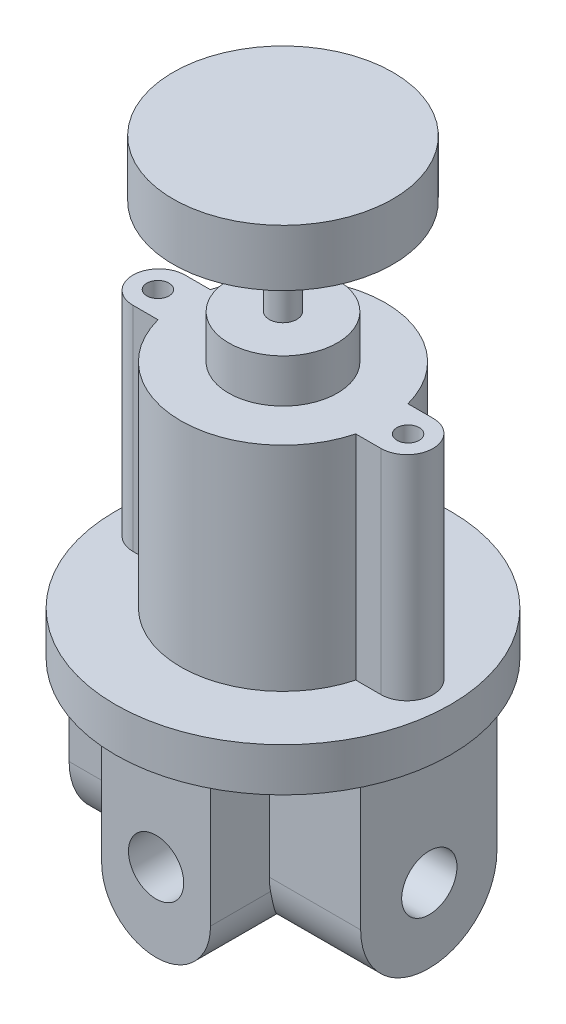
SolidWorks part; units mm, degrees
ref_plane "Front" through (0, 0, 0) normal (0, 0, 1) x (1, 0, 0)
ref_plane "Top" through (0, 0, 0) normal (0, 1, 0) x (1, 0, 0)
ref_plane "Right" through (0, 0, 0) normal (1, 0, 0) x (0, 0, -1)
ref_axis "Axis1" through (0, 0, 55) along (0, 0, -1)
sketch "Sketch1" plane through (0, 0, 0) normal (0, 1, 0) x (1, 0, 0)
  line L0 (-28.5, 0) -> (28.5, 0) construction
  line L1 (-28.5, 6) -> (-22.7211, 6)
  line L2 (-28.5, -6) -> (-22.7211, -6)
  line L3 (-34.5, 0) -> (-34.5, 13.9464) construction
  line L4 (34.5, 0) -> (34.5, 13.318) construction
  line L5 (22.7211, 6) -> (28.5, 6)
  line L6 (22.7211, -6) -> (28.5, -6)
  arc A0 (-22.7211, -6) -> (22.7211, -6) centre (0, 0) ccw
  arc A1 (-28.5, 6) -> (-28.5, -6) centre (-28.5, 0) ccw
  arc A2 (28.5, -6) -> (28.5, 6) centre (28.5, 0) ccw
  arc A3 (22.7211, 6) -> (-22.7211, 6) centre (0, 0) ccw
  point P5 (0, 0)
  dimension "D1" = 47
  dimension "D2" = 12
  dimension "D3" = 69
extrude "Boss-Extrude1" add sketch "Sketch1" against normal blind 49
hole_wizard "1/4-20 Tapped Hole1" positions "Sketch2" profile "Sketch3" tap size "1/4-20" standard "ANSI Inch" end condition up to next
sketch "Sketch2" plane through (0, 0, 0) normal (0, 1, 0) x (1, 0, 0)
  line L0 (34.5, 0) -> (-34.5, 0) construction
  line L2 (0, 0) -> (0, 23.5) construction
  arc A0 (28.5, -6) -> (28.5, 6) centre (28.5, 0) ccw construction
  arc A1 (-28.5, 6) -> (-28.5, -6) centre (-28.5, 0) ccw construction
  arc A2 (22.7211, 6) -> (-22.7211, 6) centre (0, 0) ccw construction
  point P0 (-28.75, 0)
  point P3 (28.75, 0)
  dimension "D1" = 57.5
sketch "Sketch3" plane through (-28.75, 0, 0) normal (1, 0, 0) x (0, 0, 1)
  line L0 (0, 0) -> (0, 49)
  line L1 (0, 49) -> (2.5527, 49)
  line L2 (2.5527, 49) -> (2.5527, 0)
  line L5 (2.5527, 0) -> (0, 0)
  line L11 (0, -6.35) -> (0, 107.95) construction
  dimension "Thru Tap Drill Dia." = 5.1054
  dimension "Thru Tap Drill Depth" = 49
cosmetic thread "Hole Thread1" parameters "D2"=6.35
cosmetic thread "Hole Thread2" parameters "D2"=6.35
sketch "Sketch4" plane through (0, -49, 0) normal (0, -1, 0) x (1, 0, 0)
  circle A0 centre (0, 0) radius 38.5
  dimension "D1" = 77
extrude "Boss-Extrude2" add sketch "Sketch4" along normal blind 10
sketch "Sketch5" plane through (0, -59, 0) normal (0, -1, 0) x (1, 0, 0)
  line L0 (12.5, 15.65) -> (33.5, 15.65)
  line L1 (-33.5, 15.65) -> (-12.5, 15.65)
  line L2 (-33.5, 15.65) -> (-33.5, -15.65)
  line L3 (-33.5, -15.65) -> (-12.5, -15.65)
  line L4 (33.5, 15.65) -> (33.5, -15.65)
  line L5 (-33.5, 15.65) -> (33.5, -15.65) construction
  line L6 (-33.5, -15.65) -> (33.5, 15.65) construction
  line L7 (-12.5, 29.165) -> (12.5, 29.165)
  line L8 (-12.5, 29.165) -> (-12.5, 15.65)
  line L9 (-12.5, -29.165) -> (12.5, -29.165)
  line L10 (12.5, 29.165) -> (12.5, 15.65)
  line L11 (-12.5, 29.165) -> (12.5, -29.165) construction
  line L12 (-12.5, -29.165) -> (12.5, 29.165) construction
  line L13 (-12.5, -15.65) -> (-12.5, -29.165)
  line L14 (12.5, -15.65) -> (33.5, -15.65)
  line L15 (12.5, -15.65) -> (12.5, -29.165)
  point P0 (0, 0)
  point P6 (0, 0)
  dimension "D1" = 31.3
  dimension "D2" = 67
  dimension "D3" = 25
  dimension "D4" = 58.33
extrude "Boss-Extrude3" add sketch "Sketch5" along normal blind 45
fillet "Fillet1" radius 12.5 4 edges at (12.5, -104, 22.4075) (-12.5, -104, 22.4075) (-12.5, -104, -22.4075) (12.5, -104, -22.4075)
fillet "Fillet2" radius 15.5 4 edges at (-16.75, -104, 15.65) (-16.75, -104, -15.65) (16.75, -104, 15.65) (16.75, -104, -15.65)
hole_wizard "1/2 (0.5) Diameter Hole1" positions "Sketch6" profile "Sketch7" hole size "1/2" standard "ANSI Inch" end condition up to next
sketch "Sketch6" plane through (0, 0, -29.165) normal (0, 0, -1) x (-1, 0, 0)
  line L0 (22.7211, 0) -> (-22.7211, 0) construction
  line L1 (0, -86) -> (0, 0) construction
  point P0 (0, -86)
  dimension "D1" = 86
sketch "Sketch7" plane through (0, -86, -29.165) normal (1, 0, 0) x (0, 1, 0)
  line L0 (0, 0) -> (0, 58.33)
  line L1 (0, 58.33) -> (6.35, 58.33)
  line L2 (6.35, 58.33) -> (6.35, 0)
  line L5 (6.35, 0) -> (0, 0)
  line L11 (0, -6.35) -> (0, 107.95) construction
  dimension "Thru Hole Dia." = 12.7
  dimension "Thru Hole Depth" = 58.33
hole_wizard "1/2 (0.5) Diameter Hole2" positions "Sketch8" profile "Sketch9" hole size "1/2" standard "ANSI Inch" end condition through all
sketch "Sketch8" plane through (33.5, 0, 0) normal (1, 0, 0) x (0, 0, -1)
  line L0 (0, 0) -> (0.15, -104) construction
  line L1 (6, 0) -> (-6, 0) construction
  point P0 (0.1255, -87)
  dimension "D1" = 87
sketch "Sketch9" plane through (33.5, -87, -0.1255) normal (0, 1, 0) x (0, 0, -1)
  line L0 (0, 0) -> (0, 72)
  line L1 (0, 72) -> (6.35, 72)
  line L2 (6.35, 72) -> (6.35, 0)
  line L5 (6.35, 0) -> (0, 0)
  line L11 (0, -6.35) -> (0, 107.95) construction
  dimension "Thru Hole Dia." = 12.7
  dimension "Thru Hole Depth" = 72
sketch "Sketch10" plane through (0, 0, 0) normal (0, 1, 0) x (1, 0, 0)
  circle A0 centre (0, 0) radius 12.5
  dimension "D1" = 25
extrude "Boss-Extrude4" add sketch "Sketch10" along normal blind 10
sketch "Sketch11" plane through (0, 10, 0) normal (0, 1, 0) x (1, 0, 0)
  circle A0 centre (0, 0) radius 3.175
  dimension "D1" = 6.35
extrude "Boss-Extrude5" add sketch "Sketch11" along normal blind 22
sketch "Sketch12" plane through (0, 32, 0) normal (0, 1, 0) x (1, 0, 0)
  circle A0 centre (0, 0) radius 25.25
  dimension "D1" = 50.5
extrude "Boss-Extrude6" add sketch "Sketch12" along normal blind 13
